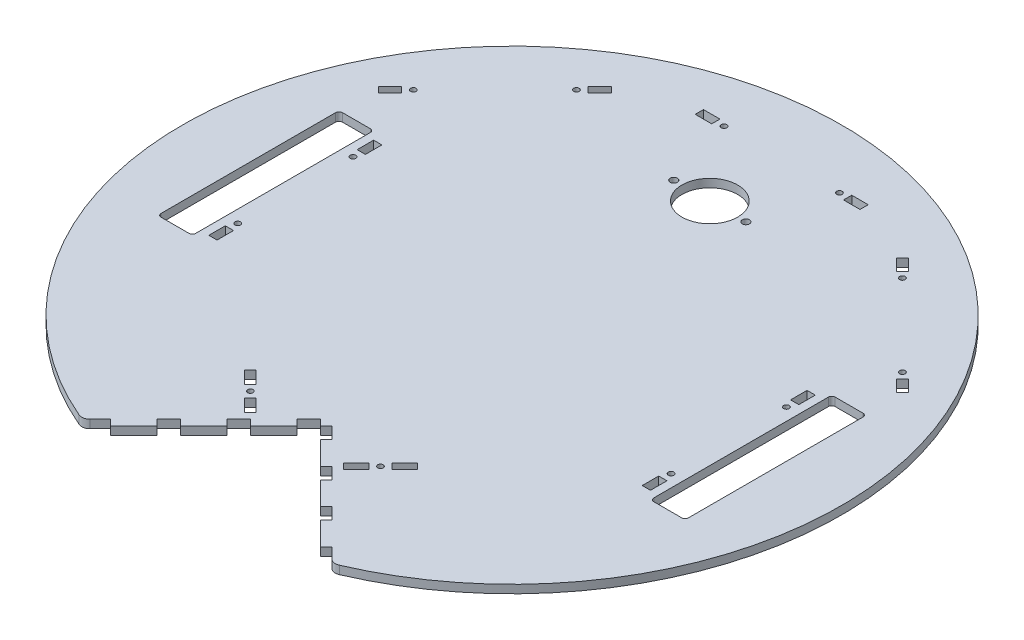
SolidWorks part; units mm, degrees
ref_plane "Front Plane" through (0, 0, 0) normal (0, 0, 1) x (1, 0, 0)
ref_plane "Top Plane" through (0, 0, 0) normal (0, 1, 0) x (1, 0, 0)
ref_plane "Right Plane" through (0, 0, 0) normal (1, 0, 0) x (0, 0, -1)
sketch "Sketch1" plane through (0, 0, 0) normal (0, 1, 0) x (1, 0, 0)
  circle A0 centre (0, 0) radius 254
  dimension "D1" = 508
extrude "Boss-Extrude1" add sketch "Sketch1" along normal blind 6.35
sketch "Sketch2" plane through (0, 6.35, 0) normal (0, 1, 0) x (1, 0, 0)
  line L0 (0, -147.7927) -> (-89.8026, -237.5952)
  line L1 (0, -36.2008) -> (0, -54.9716) construction
  line L2 (0, -147.7927) -> (89.8026, -237.5952)
  circle A0 centre (0, 0) radius 254 construction
  arc A1 (-89.8026, -237.5952) -> (89.8026, -237.5952) centre (0, 0) ccw
  dimension "D1" = 127
  dimension "D2" = 45
extrude "Cut-Extrude2" cut sketch "Sketch2" against normal through all
sketch "Sketch3" plane through (0, 6.35, 0) normal (0, 1, 0) x (1, 0, 0)
  line L0 (-31.4309, -170.2433) -> (-26.9408, -165.7532)
  line L1 (-31.4309, -170.2433) -> (-40.4112, -161.2631)
  line L2 (-26.9408, -165.7532) -> (-35.921, -156.7729)
  line L3 (-40.4112, -161.2631) -> (-35.921, -156.7729)
  line L4 (0, -147.7927) -> (-89.8026, -237.5952) construction
  line L5 (89.8026, -237.5952) -> (0, -147.7927) construction
  line L6 (-38.1661, -159.018) -> (-41.2194, -155.9647) construction
  circle A0 centre (-41.2194, -155.9647) radius 2.159
  dimension "D5" = 4.318
  dimension "D1" = 6.35
  dimension "D2" = 12.7
  dimension "D3" = 31.75
  dimension "D4" = 6.35
  dimension "D6" = 4.318
extrude "Cut-Extrude3" [suppressed] cut sketch "Sketch3" against normal through all
mirror "Mirror1" [suppressed] about plane through (0, 0, 0) normal (1, 0, 0)
sketch "Sketch4" plane through (0, 6.35, 0) normal (0, 1, 0) x (1, 0, 0)
  line L0 (0, 54.2551) -> (0, 121.7464) construction
  line L1 (-200.66, 69.85) -> (-179.07, 69.85)
  line L2 (-203.2, 67.31) -> (-203.2, -67.31)
  line L3 (-200.66, -69.85) -> (-179.07, -69.85)
  line L4 (-176.53, 67.31) -> (-176.53, -67.31)
  line L5 (-17.8666, 0) -> (24.1783, 0) construction
  line L6 (-254, -69.5481) -> (-254, -224.3367) construction
  arc A0 (-200.66, -69.85) -> (-203.2, -67.31) centre (-200.66, -67.31) cw
  arc A1 (-179.07, -69.85) -> (-176.53, -67.31) centre (-179.07, -67.31) ccw
  arc A2 (-176.53, 67.31) -> (-179.07, 69.85) centre (-179.07, 67.31) ccw
  arc A3 (-200.66, 69.85) -> (-203.2, 67.31) centre (-200.66, 67.31) ccw
  arc A4 (89.8026, -237.5952) -> (-89.8026, -237.5952) centre (0, 0) ccw construction
  dimension "D5" = 2.54
  dimension "D4" = 2.54
  dimension "D1" = 26.67
  dimension "D2" = 50.8
  dimension "D3" = 139.7
extrude "Cut-Extrude4" cut sketch "Sketch4" against normal through all
mirror "Mirror2" about plane through (0, 0, 0) normal (1, 0, 0) of "Cut-Extrude4"
sketch "Sketch6" plane through (0, 6.35, 0) normal (0, 1, 0) x (1, 0, 0)
  line L0 (-26.9408, -174.7335) -> (-85.7514, -115.9228) construction
  line L1 (0, -147.7927) -> (-89.8026, -237.5952) construction
  line L2 (89.8026, -237.5952) -> (0, -147.7927) construction
  line B0 (-52.3882, -144.7959) -> (-62.1202, -135.0639)
  line B1 (-52.3882, -144.7959) -> (-56.8783, -149.286)
  line B2 (-62.1202, -135.0639) -> (-66.6103, -139.554)
  line B3 (-56.8783, -149.286) -> (-66.6103, -139.554)
  line B4 (-43.408, -153.7761) -> (-33.676, -163.5081)
  line B5 (-47.8981, -158.2663) -> (-38.1661, -167.9983)
  line B6 (-33.676, -163.5081) -> (-38.1661, -167.9983)
  line B7 (-43.408, -153.7761) -> (-47.8981, -158.2663)
  circle B8 centre (-50.1431, -151.5311) radius 2.0955
  dimension "D1" = 38.1
  dimension "D2" = 12.7
sketch_block_instance "BoltTab-1"
sketch_block "BoltTab" parameters "D1"=4.191, "D2"=6.35, "D3"=6.35
extrude "Cut-Extrude6" cut sketch "Sketch6" against normal through all
mirror "Mirror5" about plane through (0, 0, 0) normal (1, 0, 0) of "Cut-Extrude6"
sketch "Sketch8" plane through (0, 0, 0) normal (0, -1, 0) x (1, 0, 0)
  line L0 (-170.18, -63.5) -> (-170.18, -50.8) construction
  line L1 (-170.18, -63.5) -> (-163.83, -63.5) construction
  line L2 (-163.83, -63.5) -> (-163.83, -50.8) construction
  line L3 (-170.18, -50.8) -> (-163.83, -50.8) construction
  line L4 (-170.18, -63.5) -> (-170.18, -50.8)
  line L5 (-170.18, -63.5) -> (-163.83, -63.5)
  line L6 (-163.83, -63.5) -> (-163.83, -50.8)
  line L7 (-170.18, -50.8) -> (-163.83, -50.8)
  line L8 (-170.18, 50.8) -> (-163.83, 50.8) construction
  line L9 (-170.18, 63.5) -> (-170.18, 50.8) construction
  line L10 (-163.83, 63.5) -> (-163.83, 50.8) construction
  line L11 (-170.18, 63.5) -> (-163.83, 63.5) construction
  line L12 (-170.18, 50.8) -> (-163.83, 50.8)
  line L13 (-170.18, 63.5) -> (-170.18, 50.8)
  line L14 (-163.83, 63.5) -> (-163.83, 50.8)
  line L15 (-170.18, 63.5) -> (-163.83, 63.5)
  line L16 (-170.18, -46.5836) -> (-163.83, -46.5836) construction
  line L17 (-170.18, -42.3164) -> (-163.83, -42.3164) construction
  line L18 (-170.18, -46.5836) -> (-163.83, -46.5836) construction
  line L19 (-170.18, -42.3164) -> (-163.83, -42.3164) construction
  line L20 (-167.005, -42.3164) -> (-167.005, -46.5836) construction
  line L21 (-170.18, 42.3164) -> (-163.83, 42.3164) construction
  line L22 (-170.18, 46.5836) -> (-163.83, 46.5836) construction
  line L23 (-170.18, 42.3164) -> (-163.83, 42.3164) construction
  line L24 (-170.18, 46.5836) -> (-163.83, 46.5836) construction
  line L25 (-167.005, 42.3164) -> (-167.005, 46.5836) construction
  circle A0 centre (-167.005, -44.45) radius 2.1336
  circle A1 centre (-167.005, 44.45) radius 2.1336
extrude "Cut-Extrude7" cut sketch "Sketch8" against normal through all
mirror "Mirror6" about plane through (0, 0, 0) normal (1, 0, 0) of "Cut-Extrude7"
sketch "Sketch9" plane through (0, 0, 0) normal (0, -1, 0) x (1, 0, 0)
  line L0 (-63.5, -204.6423) -> (-63.5, -210.9923) construction
  line L1 (-63.5, -204.6423) -> (-50.8, -204.6423) construction
  line L2 (-50.8, -204.6423) -> (-50.8, -210.9923) construction
  line L3 (-63.5, -210.9923) -> (-50.8, -210.9923) construction
  line L4 (-63.5, -204.6423) -> (-63.5, -210.9923)
  line L5 (-63.5, -204.6423) -> (-50.8, -204.6423)
  line L6 (-50.8, -204.6423) -> (-50.8, -210.9923)
  line L7 (-63.5, -210.9923) -> (-50.8, -210.9923)
  line L8 (-46.5836, -204.6423) -> (-46.5836, -210.9923) construction
  line L9 (-42.3164, -204.6423) -> (-42.3164, -210.9923) construction
  line L10 (-46.5836, -204.6423) -> (-46.5836, -210.9923) construction
  line L11 (-42.3164, -204.6423) -> (-42.3164, -210.9923) construction
  line L12 (-46.5836, -207.8173) -> (-42.3164, -207.8173) construction
  line L13 (42.3164, -204.6423) -> (42.3164, -210.9923) construction
  line L14 (46.5836, -204.6423) -> (46.5836, -210.9923) construction
  line L15 (42.3164, -204.6423) -> (42.3164, -210.9923) construction
  line L16 (46.5836, -204.6423) -> (46.5836, -210.9923) construction
  line L17 (50.8, -210.9923) -> (63.5, -210.9923)
  line L18 (63.5, -210.9923) -> (63.5, -204.6423)
  line L19 (63.5, -204.6423) -> (50.8, -204.6423)
  line L20 (50.8, -204.6423) -> (50.8, -210.9923)
  line L21 (50.8, -210.9923) -> (63.5, -210.9923)
  line L22 (63.5, -210.9923) -> (63.5, -204.6423)
  line L23 (63.5, -204.6423) -> (50.8, -204.6423)
  line L24 (50.8, -204.6423) -> (50.8, -210.9923)
  line L25 (42.3164, -207.8173) -> (46.5836, -207.8173) construction
  circle A0 centre (-44.45, -207.8173) radius 2.1336
  circle A1 centre (44.45, -207.8173) radius 2.1336
  dimension "D1" = 0
extrude "Cut-Extrude8" cut sketch "Sketch9" against normal through all
sketch "Sketch10" plane through (0, 0, 0) normal (0, -1, 0) x (1, 0, 0)
  line L0 (-204.1857, -101.143) -> (-195.2055, -110.1232) construction
  line L1 (-195.2055, -110.1232) -> (-190.7153, -105.6331) construction
  line L2 (-190.7153, -105.6331) -> (-199.6956, -96.6529) construction
  line L3 (-199.6956, -96.6529) -> (-204.1857, -101.143) construction
  line L4 (-123.3634, -181.9653) -> (-114.3832, -190.9455) construction
  line L5 (-114.3832, -190.9455) -> (-109.893, -186.4554) construction
  line L6 (-109.893, -186.4554) -> (-118.8733, -177.4752) construction
  line L7 (-118.8733, -177.4752) -> (-123.3634, -181.9653) construction
  line L8 (-204.1857, -101.143) -> (-195.2055, -110.1232)
  line L9 (-195.2055, -110.1232) -> (-190.7153, -105.6331)
  line L10 (-190.7153, -105.6331) -> (-199.6956, -96.6529)
  line L11 (-199.6956, -96.6529) -> (-204.1857, -101.143)
  line L12 (-123.3634, -181.9653) -> (-114.3832, -190.9455)
  line L13 (-114.3832, -190.9455) -> (-109.893, -186.4554)
  line L14 (-109.893, -186.4554) -> (-118.8733, -177.4752)
  line L15 (-118.8733, -177.4752) -> (-123.3634, -181.9653)
  line L16 (-187.7339, -108.6146) -> (-192.224, -113.1047) construction
  line L17 (-184.7165, -111.6319) -> (-189.2067, -116.122) construction
  line L18 (-124.8721, -171.4763) -> (-129.3622, -175.9665) construction
  line L19 (-121.8547, -174.4937) -> (-126.3449, -178.9838) construction
  line L20 (-187.7339, -108.6146) -> (-192.224, -113.1047) construction
  line L21 (-184.7165, -111.6319) -> (-189.2067, -116.122) construction
  line L22 (-124.8721, -171.4763) -> (-129.3622, -175.9665) construction
  line L23 (-121.8547, -174.4937) -> (-126.3449, -178.9838) construction
  line L25 (-186.9616, -113.877) -> (-189.979, -110.8596) construction
  line L26 (-127.1172, -173.7214) -> (-124.0998, -176.7388) construction
  circle A0 centre (-188.4703, -112.3683) radius 2.1336
  circle A1 centre (-125.6085, -175.2301) radius 2.1336
extrude "Cut-Extrude9" cut sketch "Sketch10" against normal through all
mirror "Mirror7" about plane through (0, 0, 0) normal (1, 0, 0) of "Cut-Extrude9"
sketch "Sketch11" plane through (0, 6.35, 0) normal (0, 1, 0) x (1, 0, 0)
  line L0 (0, 61.4305) -> (0, 100.7164) construction
  line L1 (-82.8279, 254) -> (68.7629, 254) construction
  circle A0 centre (0, 152.4) radius 21.463
  arc A1 (89.8026, -237.5952) -> (-89.8026, -237.5952) centre (0, 0) ccw construction
  circle A2 centre (27.7813, 152.4) radius 2.7781 construction
  circle A3 centre (-27.7813, 152.4) radius 2.7781 construction
  circle A4 centre (27.7813, 152.4) radius 2.7781
  circle A5 centre (-27.7813, 152.4) radius 2.7781
  dimension "D1" = 42.926
  dimension "D2" = 101.6
extrude "Cut-Extrude10" cut sketch "Sketch11" against normal through all
sketch "Sketch12" plane through (73.8963, 0, 73.8963) normal (0.7071, 0, 0.7071) x (0.7071, 0, -0.7071)
  line L0 (-218.8052, 6.35) -> (-218.8052, 0) construction
  line L1 (-244.2052, 6.35) -> (-218.8052, 6.35)
  line L2 (-244.2052, 6.35) -> (-244.2052, 0)
  line L3 (-244.2052, 0) -> (-218.8052, 0)
  line L4 (-218.8052, 6.35) -> (-218.8052, 0)
  line L5 (-104.5052, 0) -> (-231.5052, 0) construction
  line L6 (-104.5052, 6.35) -> (-231.5052, 6.35) construction
  line L7 (-193.4052, 6.35) -> (-180.7052, 6.35)
  line L8 (-193.4052, 6.35) -> (-193.4052, 0)
  line L9 (-193.4052, 0) -> (-180.7052, 0)
  line L10 (-180.7052, 6.35) -> (-180.7052, 0)
  line L11 (-193.4052, 0) -> (-193.4052, 6.35) construction
  line L12 (-180.7052, 6.35) -> (-180.7052, 0) construction
  line L13 (-155.3052, 0) -> (-155.3052, 6.35) construction
  line L14 (-155.3052, 6.35) -> (-142.6052, 6.35)
  line L15 (-155.3052, 6.35) -> (-155.3052, 0)
  line L16 (-155.3052, 0) -> (-142.6052, 0)
  line L17 (-142.6052, 6.35) -> (-142.6052, 0)
  line L18 (-142.6052, 6.35) -> (-142.6052, 0) construction
  line L19 (-117.2052, 0) -> (-117.2052, 6.35) construction
  line L20 (-117.2052, 6.35) -> (-104.5052, 6.35)
  line L21 (-117.2052, 6.35) -> (-117.2052, 0)
  line L22 (-117.2052, 0) -> (-104.5052, 0)
  line L23 (-104.5052, 6.35) -> (-104.5052, 0)
  dimension "D1" = 25.4
extrude "Cut-Extrude11" cut sketch "Sketch12" against normal blind 6.35
mirror "Mirror8" about plane through (0, 0, 0) normal (1, 0, 0) of "Cut-Extrude11"
fillet "Fillet1" radius 6.35 2 edges at (96.2464, 3.175, 235.0588) (-96.2464, 3.175, 235.0588)
